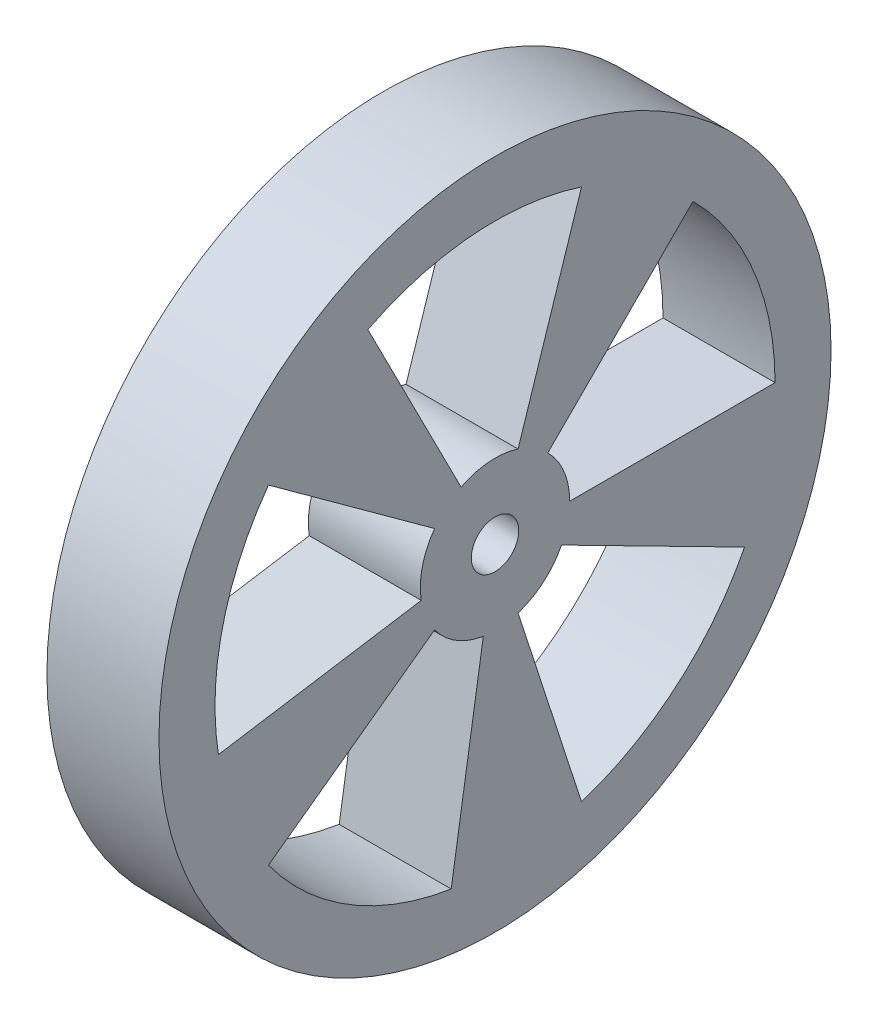
SolidWorks part; units mm, degrees
ref_plane "Front Plane" through (0, 0, 0) normal (0, 0, 1) x (1, 0, 0)
ref_plane "Top Plane" through (0, 0, 0) normal (0, 1, 0) x (1, 0, 0)
ref_plane "Right Plane" through (0, 0, 0) normal (1, 0, 0) x (0, 0, -1)
sketch "Sketch1" plane through (0, 0, 0) normal (1, 0, 0) x (0, 0, -1)
  circle A0 centre (0, 0) radius 90
  dimension "D1" = 180
extrude "Boss-Extrude1" add sketch "Sketch1" along normal blind 30
sketch "Sketch2" plane through (0, 0, 0) normal (-1, 0, 0) x (0, 0, 1)
  circle A0 centre (0, 0) radius 6.35
  dimension "D1" = 12.7
extrude "Cut-Extrude2" cut sketch "Sketch2" against normal through all
sketch "Sketch3" plane through (0, 0, 0) normal (-1, 0, 0) x (0, 0, 1)
  line L0 (-20, 0) -> (-75, 0)
  line L1 (-53.033, 53.033) -> (-14.1421, 14.1421)
  arc A0 (-75, 0) -> (-53.033, 53.033) centre (0, 0) cw
  arc A1 (-14.1421, 14.1421) -> (-20, 0) centre (0, 0) ccw
  dimension "D1" = 20
  dimension "D2" = 75
  dimension "D3" = 45
extrude "Cut-Extrude3" cut sketch "Sketch3" against normal blind 30
pattern_circular "CirPattern1" count 5 over 360 about axis through (30, 0, 0) along (-1, 0, 0) of "Cut-Extrude3" reverse direction yes
